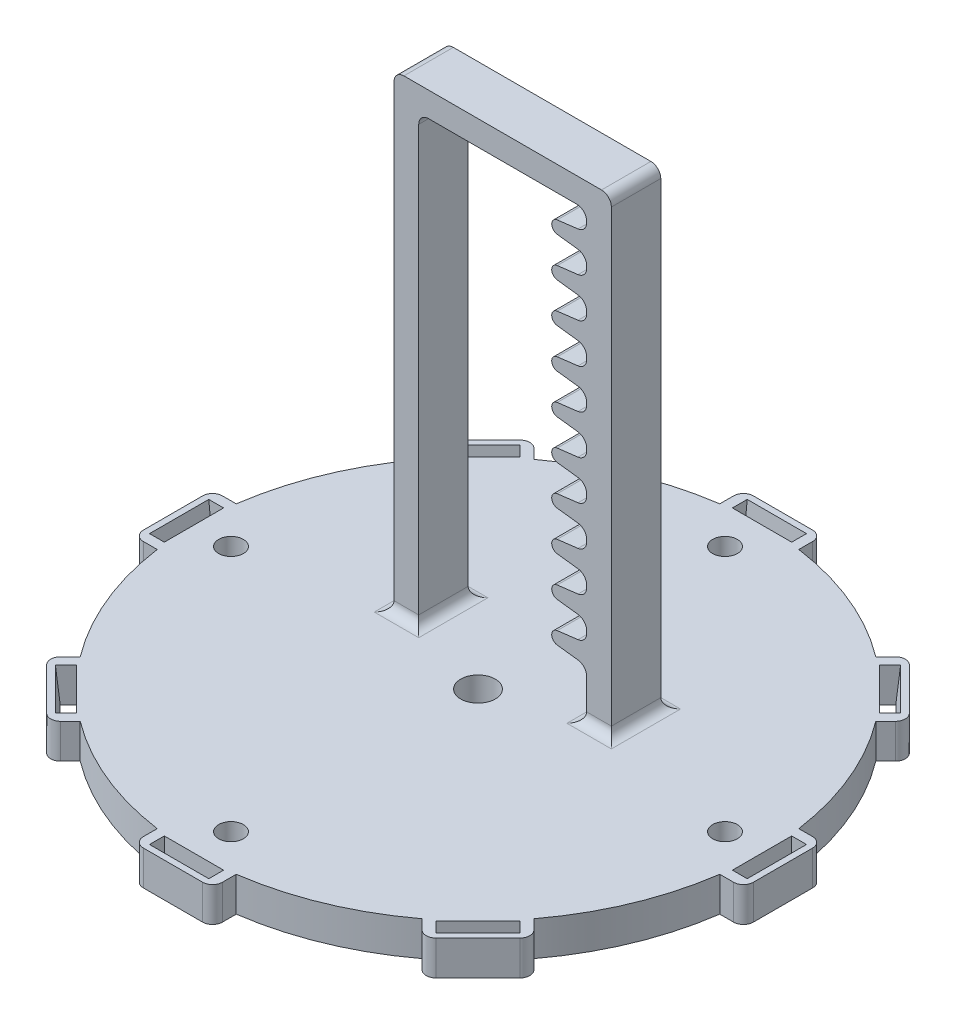
SolidWorks part; units mm, degrees
ref_plane "Front Plane" through (0, 0, 0) normal (0, 0, 1) x (1, 0, 0)
ref_plane "Top Plane" through (0, 0, 0) normal (0, 1, 0) x (1, 0, 0)
ref_plane "Right Plane" through (0, 0, 0) normal (1, 0, 0) x (0, 0, -1)
sketch "Sketch1" plane through (0, 0, 0) normal (0, 1, 0) x (1, 0, 0)
  line L0 (-8, 56.9408) -> (-8, 59.7408)
  line L1 (0, 57.5) -> (0, -57.5) construction
  line L2 (8, 56.9408) -> (8, 59.7408)
  line L3 (-6, 61.7408) -> (6, 61.7408)
  line L4 (39.4147, 47.8999) -> (47.8999, 39.4147)
  line L9 (34.6063, 45.9201) -> (36.5862, 47.8999)
  line L10 (45.9201, 34.6063) -> (47.8999, 36.5862)
  line L15 (61.7408, 6) -> (61.7408, -6)
  line L16 (56.9408, 8) -> (59.7408, 8)
  line L17 (56.9408, -8) -> (59.7408, -8)
  line L22 (47.8999, -39.4147) -> (39.4147, -47.8999)
  line L23 (45.9201, -34.6063) -> (47.8999, -36.5862)
  line L24 (34.6063, -45.9201) -> (36.5862, -47.8999)
  line L29 (6, -61.7408) -> (-6, -61.7408)
  line L30 (8, -56.9408) -> (8, -59.7408)
  line L31 (-8, -56.9408) -> (-8, -59.7408)
  line L36 (-39.4147, -47.8999) -> (-47.8999, -39.4147)
  line L37 (-34.6063, -45.9201) -> (-36.5862, -47.8999)
  line L38 (-45.9201, -34.6063) -> (-47.8999, -36.5862)
  line L43 (-61.7408, -6) -> (-61.7408, 6)
  line L44 (-56.9408, -8) -> (-59.7408, -8)
  line L45 (-56.9408, 8) -> (-59.7408, 8)
  line L50 (-47.8999, 39.4147) -> (-39.4147, 47.8999)
  line L51 (-45.9201, 34.6063) -> (-47.8999, 36.5862)
  line L52 (-34.6063, 45.9201) -> (-36.5862, 47.8999)
  arc A0 (-8, 56.9408) -> (-34.6063, 45.9201) centre (0, 0) ccw
  arc A1 (6, 61.7408) -> (8, 59.7408) centre (6, 59.7408) cw
  arc A2 (-6, 61.7408) -> (-8, 59.7408) centre (-6, 59.7408) ccw
  arc A3 (39.4147, 47.8999) -> (36.5862, 47.8999) centre (38.0005, 46.4857) ccw
  arc A4 (47.8999, 39.4147) -> (47.8999, 36.5862) centre (46.4857, 38.0005) cw
  arc A5 (61.7408, 6) -> (59.7408, 8) centre (59.7408, 6) ccw
  arc A6 (61.7408, -6) -> (59.7408, -8) centre (59.7408, -6) cw
  arc A7 (47.8999, -39.4147) -> (47.8999, -36.5862) centre (46.4857, -38.0005) ccw
  arc A8 (39.4147, -47.8999) -> (36.5862, -47.8999) centre (38.0005, -46.4857) cw
  arc A9 (6, -61.7408) -> (8, -59.7408) centre (6, -59.7408) ccw
  arc A10 (-6, -61.7408) -> (-8, -59.7408) centre (-6, -59.7408) cw
  arc A11 (-39.4147, -47.8999) -> (-36.5862, -47.8999) centre (-38.0005, -46.4857) ccw
  arc A12 (-47.8999, -39.4147) -> (-47.8999, -36.5862) centre (-46.4857, -38.0005) cw
  arc A13 (-61.7408, -6) -> (-59.7408, -8) centre (-59.7408, -6) ccw
  arc A14 (-61.7408, 6) -> (-59.7408, 8) centre (-59.7408, 6) cw
  arc A15 (-47.8999, 39.4147) -> (-47.8999, 36.5862) centre (-46.4857, 38.0005) ccw
  arc A16 (-39.4147, 47.8999) -> (-36.5862, 47.8999) centre (-38.0005, 46.4857) cw
  arc A17 (-45.9201, 34.6063) -> (-56.9408, 8) centre (0, 0) ccw
  arc A18 (-56.9408, -8) -> (-45.9201, -34.6063) centre (0, 0) ccw
  arc A19 (34.6063, 45.9201) -> (8, 56.9408) centre (0, 0) ccw
  arc A20 (-34.6063, -45.9201) -> (-8, -56.9408) centre (0, 0) ccw
  arc A21 (8, -56.9408) -> (34.6063, -45.9201) centre (0, 0) ccw
  arc A22 (45.9201, -34.6063) -> (56.9408, -8) centre (0, 0) ccw
  arc A23 (56.9408, 8) -> (45.9201, 34.6063) centre (0, 0) ccw
  point P11 (8, 61.7408)
  point P14 (-8, 61.7408)
  point P17 (-8, 58.3408)
  point P98 (0, 0)
  dimension "D1" = 115
  dimension "D2" = 2
  dimension "D3" = 16
  dimension "D4" = 2.8
  dimension "D7" = 8
extrude "Boss-Extrude1" add sketch "Sketch1" along normal blind 7
sketch "Sketch2" plane through (0, 7, 0) normal (0, 1, 0) x (1, 0, 0)
  line L0 (-57.5, 0) -> (57.5, 0) construction
  line L1 (0, 0) -> (0, 10) construction
  line L7 (17, 5) -> (22, 5)
  line L14 (0, 10) -> (29.7122, 10) construction
  line L15 (0, 10) -> (-19.5, 10) construction
  line L17 (17, 5) -> (17, 15)
  line L18 (-22, 15) -> (-17, 15)
  line L19 (-22, 15) -> (-22, 5)
  line L20 (-22, 5) -> (-17, 5)
  line L21 (-17, 15) -> (-17, 5)
  line L22 (-22, 15) -> (-17, 5) construction
  line L23 (-22, 5) -> (-17, 15) construction
  line L24 (17, 15) -> (22, 15)
  line L25 (22, 5) -> (22, 15)
  line L26 (17, 5) -> (22, 15) construction
  line L27 (17, 15) -> (22, 5) construction
  circle A0 centre (0, 0) radius 57.5 construction
  point P8 (19.5, 10)
  dimension "D1" = 10
  dimension "D2" = 17
  dimension "D3" = 17
  dimension "D4" = 10
  dimension "D5" = 5
  dimension "D6" = 10
  dimension "D7" = 5
extrude "Boss-Extrude2" add sketch "Sketch2" along normal blind 95
sketch "Sketch15" plane through (0, 0, 0) normal (0, -1, 0) x (1, 0, 0)
  circle A0 centre (0, 0) radius 3.5
  dimension "D1" = 7
extrude "Cut-Extrude3" cut sketch "Sketch15" along direction (0, 1, 0) on the side against the normal up to surface (7 mm away) contours A0 up to face at (0, 7, 0)
sketch "Sketch16" plane through (0, 0, 0) normal (0, -1, 0) x (1, 0, 0)
  line L1 (-6, 59.8) -> (6, 59.8)
  line L2 (-6, 59.8) -> (-6, 57.5)
  line L3 (-6, 57.5) -> (6, 57.5)
  line L4 (6, 59.8) -> (6, 57.5)
  point P5 (0, 57.5)
  dimension "D1" = 2.3
  dimension "D2" = 12
  dimension "D3" = 57.5
sketch "Sketch17" plane through (0, 7, 0) normal (0, 1, 0) x (1, 0, 0)
  line L0 (-6, -57.5) -> (6, -57.5) construction
  line L1 (-6, -57.5) -> (6, -57.5)
  line L2 (-6, -57.5) -> (-6, -60.5)
  line L3 (-6, -60.5) -> (6, -60.5)
  line L4 (6, -60.5) -> (6, -57.5)
  dimension "D1" = 3
ref_axis "Axis1" through (0, 107.1, 0) along (0, -1, 0)
loft "Cut-Loft2" cut profiles "Sketch16", "Sketch17" connector at (6, 0, 59.8) connector at (6, 7, 60.5)
pattern_circular "CirPattern1" count 8 over 360 about axis through (0, 107.1, 0) along (0, -1, 0) of "Cut-Loft2"
sketch "Sketch18" plane through (-17, 0, 0) normal (1, 0, 0) x (0, 0, -1)
  line L0 (15, 102) -> (15, 7) construction
  line L1 (5, 102) -> (15, 102)
  line L2 (5, 102) -> (5, 97)
  line L3 (5, 97) -> (15, 97)
  line L4 (15, 102) -> (15, 97)
  dimension "D1" = 5
extrude "Boss-Extrude3" add sketch "Sketch18" along normal up to surface (34 mm away) up to face at (17, 54.5, -10)
sketch "Sketch19" plane through (0, 0, -15) normal (0, 0, -1) x (-1, 0, 0)
  line L0 (-17, 93) -> (-11.0447, 92.2688)
  line L1 (-17, 97) -> (-17, 7) construction
  line L4 (-11, 91) -> (-19.8185, 91) construction
  line L5 (-17, 89) -> (-11.0447, 89.7312)
  line L6 (-17, 93) -> (-17, 89)
  arc A1 (-11.0447, 92.2688) -> (-11.0447, 89.7312) centre (-11.2005, 91) cw
  dimension "D1" = 6
  dimension "D4" = 4
  dimension "D2" = 7
  dimension "D3" = 4
extrude "Boss-Extrude4" add sketch "Sketch19" against normal blind 10
fillet "Fillet1" radius 2 2 edges at (17, 93, -10) (17, 89, -10)
fillet "Fillet2" radius 2 12 edges at (-22, 102, -10) (22, 102, -10) (17, 7, -10) (19.5, 7, -15) (19.5, 7, -5) (22, 7, -10) (-19.5, 7, -5) (-19.5, 7, -15) (-22, 7, -10) (-17, 7, -10) (-17, 97, -10) (17, 97, -10)
pattern_linear "LPattern2" count 10 spacing 8 along (0, -1, 0) of "Fillet1", "Boss-Extrude4"
sketch "Sketch20" plane through (0, 7, 0) normal (0, 1, 0) x (1, 0, 0)
  line L0 (0, 0) -> (0, 50) construction
  circle A0 centre (0, 50) radius 2.5
  dimension "D2" = 5
  dimension "D1" = 50
extrude "Cut-Extrude4" cut sketch "Sketch20" against normal blind 10
pattern_circular "CirPattern2" count 4 over 360 about axis through (0, 107.1, 0) along (0, -1, 0) of "Cut-Extrude4"
equation "\"85.00.00mm\"=8500"
